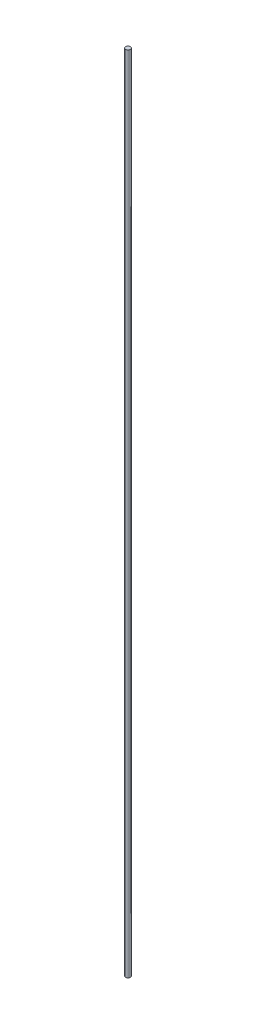
SolidWorks part; units mm, degrees
material "Balsa"
ref_plane "Front Plane" through (0, 0, 0) normal (0, 0, 1) x (1, 0, 0)
ref_plane "Top Plane" through (0, 0, 0) normal (0, 1, 0) x (1, 0, 0)
ref_plane "Right Plane" through (0, 0, 0) normal (1, 0, 0) x (0, 0, -1)
sketch "Sketch1" plane through (0, 0, 0) normal (0, 1, 0) x (1, 0, 0)
  circle A0 centre (0, 0) radius 3
  dimension "D1" = 6
extrude "Boss-Extrude1" add sketch "Sketch1" along normal blind 1000
sketch "Sketch2" plane through (0, 1000, 0) normal (0, 1, 0) x (1, 0, 0)
extrude "Boss-Extrude2" add sketch "Sketch1<2>" against normal blind 6
sketch "Sketch1<2>" plane through (0, 0, 0) normal (0, 1, 0) x (1, 0, 0) same geometry as "Sketch1"
